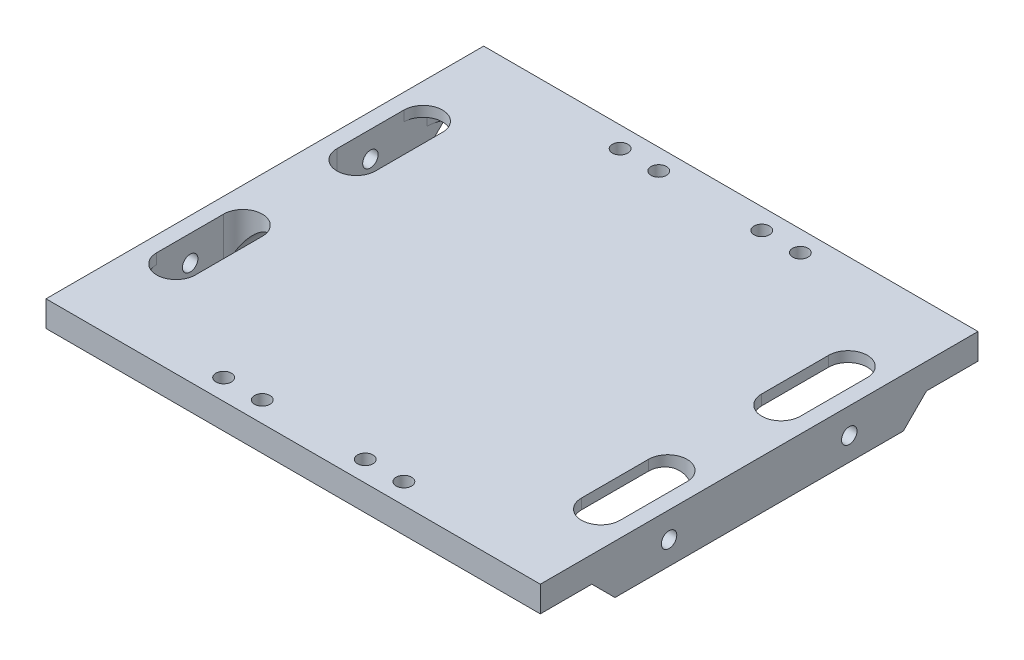
SolidWorks part; units mm, degrees
ref_plane "Front Plane" through (0, 0, 0) normal (0, 0, 1) x (1, 0, 0)
ref_plane "Top Plane" through (0, 0, 0) normal (0, 1, 0) x (1, 0, 0)
ref_plane "Right Plane" through (0, 0, 0) normal (1, 0, 0) x (0, 0, -1)
sketch "Sketch1" plane through (0, 0, 0) normal (0, 0, 1) x (1, 0, 0)
  line L0 (-45, 0) -> (45, 0)
  line L6 (45, -7.5) -> (48, -7.5)
  line L11 (48, -7.5) -> (48, 2)
  line L12 (48, 2) -> (-48, 2)
  line L13 (-48, 2) -> (-48, -7.5)
  line L14 (-48, -7.5) -> (-45, -7.5)
  line L18 (-45, -7.5) -> (-45, 0)
  line L20 (45, -7.5) -> (45, 0)
  point P0 (0, 0)
  dimension "D2" = 7.5
  dimension "D3" = 2
  dimension "D4" = 96
  dimension "D5" = 48
  dimension "D1" = 3
extrude "Boss-Extrude1" add sketch "Sketch1" along normal blind 85
sketch "Sketch3" plane through (-48, 0, 0) normal (-1, 0, 0) x (0, 0, 1)
  line L0 (0, -3) -> (85, -3) construction
  line L1 (0, 2) -> (0, -7.5) construction
  line L2 (85, 2) -> (85, -7.5) construction
  line L3 (85, 2) -> (0, 2) construction
  circle A0 centre (25, -3) radius 1.5
  circle A1 centre (60, -3) radius 1.5
  point P10 (0, 0)
  point P11 (0, 0)
  dimension "D1" = 3
  dimension "D2" = 5
  dimension "D3" = 35
  dimension "D4" = 85
  dimension "D5" = 25
extrude "Cut-Extrude2" cut sketch "Sketch3" against normal through all
sketch "Sketch4" plane through (0, 2, 0) normal (0, 1, 0) x (1, 0, 0)
  line L0 (-41.25, -18.5) -> (-41.25, -66.5) construction
  line L5 (-37.5, -18.5) -> (-37.5, -31.5)
  line L6 (-45, -18.5) -> (-45, -31.5)
  line L11 (41.25, -18.5) -> (41.25, -66.5) construction
  line L12 (45, 0) -> (-45, 0)
  line L13 (45, -85) -> (45, 0)
  line L14 (45, -85) -> (45, -53.5)
  line L15 (-45, 0) -> (-45, -85)
  line L16 (-45, 0) -> (-45, -31.5)
  line L17 (-45, -53.5) -> (-45, -66.5)
  line L18 (-45, -85) -> (45, -85)
  line L19 (-45, -53.5) -> (-45, -85)
  line L20 (-37.5, -53.5) -> (-37.5, -66.5)
  line L21 (37.5, -53.5) -> (37.5, -66.5)
  line L22 (45, -31.5) -> (45, 0)
  line L23 (45, -53.5) -> (45, -66.5)
  line L24 (45, 0) -> (-45, 0)
  line L30 (-45, -85) -> (45, -85)
  line L36 (45, -18.5) -> (45, -31.5)
  line L37 (37.5, -18.5) -> (37.5, -31.5)
  line L38 (48, -61.5) -> (48, -58.5) construction
  line L39 (48, -26.5) -> (48, -23.5) construction
  line L40 (-48, -23.5) -> (-48, -26.5) construction
  line L41 (-48, -58.5) -> (-48, -61.5) construction
  line L42 (48, -61.5) -> (48, -58.5)
  line L43 (48, -26.5) -> (48, -23.5)
  line L44 (-48, -23.5) -> (-48, -26.5)
  line L45 (-48, -58.5) -> (-48, -61.5)
  arc A0 (-37.5, -18.5) -> (-45, -18.5) centre (-41.25, -18.5) ccw
  arc A1 (-45, -66.5) -> (-37.5, -66.5) centre (-41.25, -66.5) ccw
  arc A2 (45, -18.5) -> (37.5, -18.5) centre (41.25, -18.5) ccw
  arc A3 (37.5, -66.5) -> (45, -66.5) centre (41.25, -66.5) ccw
  arc A4 (-37.5, -53.5) -> (-45, -53.5) centre (-41.25, -53.5) ccw
  arc A5 (-45, -31.5) -> (-37.5, -31.5) centre (-41.25, -31.5) ccw
  arc A6 (45, -53.5) -> (37.5, -53.5) centre (41.25, -53.5) ccw
  arc A7 (37.5, -31.5) -> (45, -31.5) centre (41.25, -31.5) ccw
  point P11 (-41.25, -42.5)
  point P15 (40.4085, -33.194)
  point P21 (-41.25, -48.9364)
  point P26 (-41.25, -50.8182)
  point P27 (41.25, -42.5)
  point P30 (-40.1806, -58.8985)
  point P33 (0, 0)
  point P35 (41.25, -48.9364)
  point P44 (41.25, -53.5)
  point P45 (41.25, -53.5)
  dimension "D2" = 7.5
  dimension "D3" = 85
  dimension "D4" = 5
  dimension "D6" = 5
  dimension "D7" = 5
  dimension "D8" = 5
extrude "Cut-Extrude3" cut sketch "Sketch4" against normal through all contours L20 A4 L17 A1 | L6 A5 L5 A0 | L37 A7 L22 A2 | L14 A6 L21 A3 region at (-41.25, 2, 25) region at (-41.25, 2, 60) region at (41.25, 2, 25) region at (41.25, 2, 60)
sketch "Sketch5" plane through (0, 0, 0) normal (0, -1, 0) x (1, 0, 0)
  line L0 (-45, 85) -> (45, 85) construction
  line L1 (-45, 85) -> (45, 85)
  line L3 (-45, 77) -> (45, 77)
  line L5 (-45, 85) -> (45, 77) construction
  line L6 (-45, 77) -> (45, 85) construction
  line L9 (-45, 0) -> (45, 0) construction
  line L10 (-45, 0) -> (45, 0)
  line L12 (-45, 8) -> (45, 8)
  line L14 (-45, 0) -> (45, 8) construction
  line L15 (-45, 8) -> (45, 0) construction
  line L18 (-45, 85) -> (-45, 77)
  line L19 (45, 0) -> (45, 8)
  line L20 (-45, 8) -> (-45, 0)
  line L21 (45, 77) -> (45, 85)
  line L22 (-45, 85) -> (-45, 0) construction
  line L23 (45, 85) -> (45, 0) construction
  point P4 (0, 81)
  point P15 (0, 4)
  dimension "D1" = 8
extrude "Boss-Extrude2" add sketch "Sketch5" along normal blind 3
sketch "Sketch6" plane through (0, 2, 0) normal (0, 1, 0) x (1, 0, 0)
  line L0 (-48, -4) -> (48, -4) construction
  line L1 (-48, -85) -> (-48, 0) construction
  line L2 (48, -85) -> (48, 0) construction
  line L3 (-48, -81) -> (48, -81) construction
  line L4 (48, 0) -> (-48, 0) construction
  line L5 (48, -85) -> (-48, -85) construction
  circle A0 centre (-17.5, -4) radius 1.5
  circle A1 centre (17.5, -4) radius 1.5
  circle A2 centre (-17.5, -81) radius 1.5
  circle A3 centre (17.5, -81) radius 1.5
  circle A4 centre (-10, -4) radius 1.5
  circle A5 centre (10, -4) radius 1.5
  circle A6 centre (-10, -81) radius 1.5
  circle A7 centre (10, -81) radius 1.5
  point P28 (0, 0)
  point P29 (0, 0)
  point P30 (0, 0)
  point P31 (0, 0)
  point P34 (-6.3527, -4)
  dimension "D3" = 3
  dimension "D1" = 4
  dimension "D2" = 4
  dimension "D4" = 7.5
  dimension "D5" = 7.5
  dimension "D6" = 7.5
  dimension "D7" = 7.5
  dimension "D8" = 20
  dimension "D9" = 96
  dimension "D10" = 38
  dimension "D11" = 20
  dimension "D12" = 38
extrude "Cut-Extrude4" cut sketch "Sketch6" against normal through all
fillet "Fillet4" radius 6 4 edges at (45, -1.5, 77) (-45, -1.5, 77) (-45, -1.5, 8) (45, -1.5, 8)
fillet "Fillet5" radius 7.5 2 edges at (45, 0, 42.5) (-45, 0, 42.5)
sketch "Sketch7" plane through (48, 0, 0) normal (1, 0, 0) x (0, 0, -1)
  line L0 (0, -7.5) -> (-31.5, -7.5) construction
  line L1 (-31.5, -7.5) -> (-31.5, 2) construction
  line L2 (-31.5, 2) -> (-18.5, 2) construction
  line L3 (-18.5, 2) -> (-18.5, 0) construction
  line L4 (-18.5, 0) -> (-14, 0) construction
  line L5 (-14, 0) -> (-14, -3) construction
  line L6 (-14, -3) -> (0, -3) construction
  line L7 (0, -3) -> (0, -7.5) construction
  line L8 (-53.5, 2) -> (-53.5, -7.5) construction
  line L9 (-53.5, -7.5) -> (-85, -7.5) construction
  line L10 (-85, -7.5) -> (-85, -3) construction
  line L11 (-85, -3) -> (-71, -3) construction
  line L12 (-71, -3) -> (-71, 0) construction
  line L13 (-71, 0) -> (-66.5, 0) construction
  line L14 (-66.5, 0) -> (-66.5, 2) construction
  line L15 (-66.5, 2) -> (-53.5, 2) construction
  line L16 (0, -7.5) -> (-31.5, -7.5) construction
  line L17 (-31.5, -7.5) -> (-31.5, 2) construction
  line L18 (-31.5, 2) -> (-18.5, 2) construction
  line L19 (-18.5, 2) -> (-18.5, 0) construction
  line L20 (-18.5, 0) -> (-14, 0) construction
  line L21 (-14, 0) -> (-14, -3) construction
  line L22 (-14, -3) -> (0, -3) construction
  line L23 (0, -3) -> (0, -7.5) construction
  line L24 (-53.5, 2) -> (-53.5, -7.5) construction
  line L25 (-53.5, -7.5) -> (-85, -7.5) construction
  line L26 (-85, -7.5) -> (-85, -3) construction
  line L27 (-85, -3) -> (-71, -3) construction
  line L28 (-71, -3) -> (-71, 0) construction
  line L29 (-71, 0) -> (-66.5, 0) construction
  line L30 (-66.5, 0) -> (-66.5, 2) construction
  line L31 (-66.5, 2) -> (-53.5, 2) construction
  line L32 (-85, -3) -> (-71, -3)
  line L34 (-63.2058, -7.5) -> (-85, -7.5)
  line L35 (-85, -7.5) -> (-85, -3)
  line L36 (0, -7.5) -> (-21.7942, -7.5)
  line L38 (-14, -3) -> (0, -3)
  line L39 (0, -3) -> (0, -7.5)
  line L42 (-75, -3) -> (-70.5, -7.5)
  line L43 (-10, -3) -> (-14.5, -7.5)
  line M8 (0, -7.5) -> (0, 2)
  line M10 (-85, 2) -> (-85, -7.5)
  line M11 (-85, -7.5) -> (0, -7.5)
  dimension "D1" = 45
  dimension "D2" = 45
  dimension "D3" = 10
extrude "Cut-Extrude5" cut sketch "Sketch7" against normal through all contours L42 L32 M10 M11 | L38 L43 L36 M8 region at (48, -5.3878, 6.1939) region at (48, -5.3878, 78.8061)
equation "\"D5@Sketch1\"=\"D4@Sketch1\"/2"
equation "\"D5@Sketch3\"=(\"D4@Sketch3\"-\"D3@Sketch3\")/2"
equation "\"D2@Sketch6\"=\"D1@Sketch6\""
equation "\"D5@Sketch6\"=\"D4@Sketch6\""
equation "\"D6@Sketch6\"=\"D4@Sketch6\""
equation "\"D7@Sketch6\"=\"D4@Sketch6\""
equation "\"D10@Sketch6\"=(\"D9@Sketch6\"-\"D8@Sketch6\")/2"
equation "\"D11@Sketch6\"=\"D8@Sketch6\""
equation "\"D12@Sketch6\"=\"D10@Sketch6\""
equation "\"D5@Sketch4\"=\"D4@Sketch4\""
equation "\"D6@Sketch4\"=\"D4@Sketch4\""
equation "\"D7@Sketch4\"=\"D4@Sketch4\""
equation "\"D8@Sketch4\"=\"D4@Sketch4\""
equation "\"D4@Sketch7\"=\"D3@Sketch7\""
